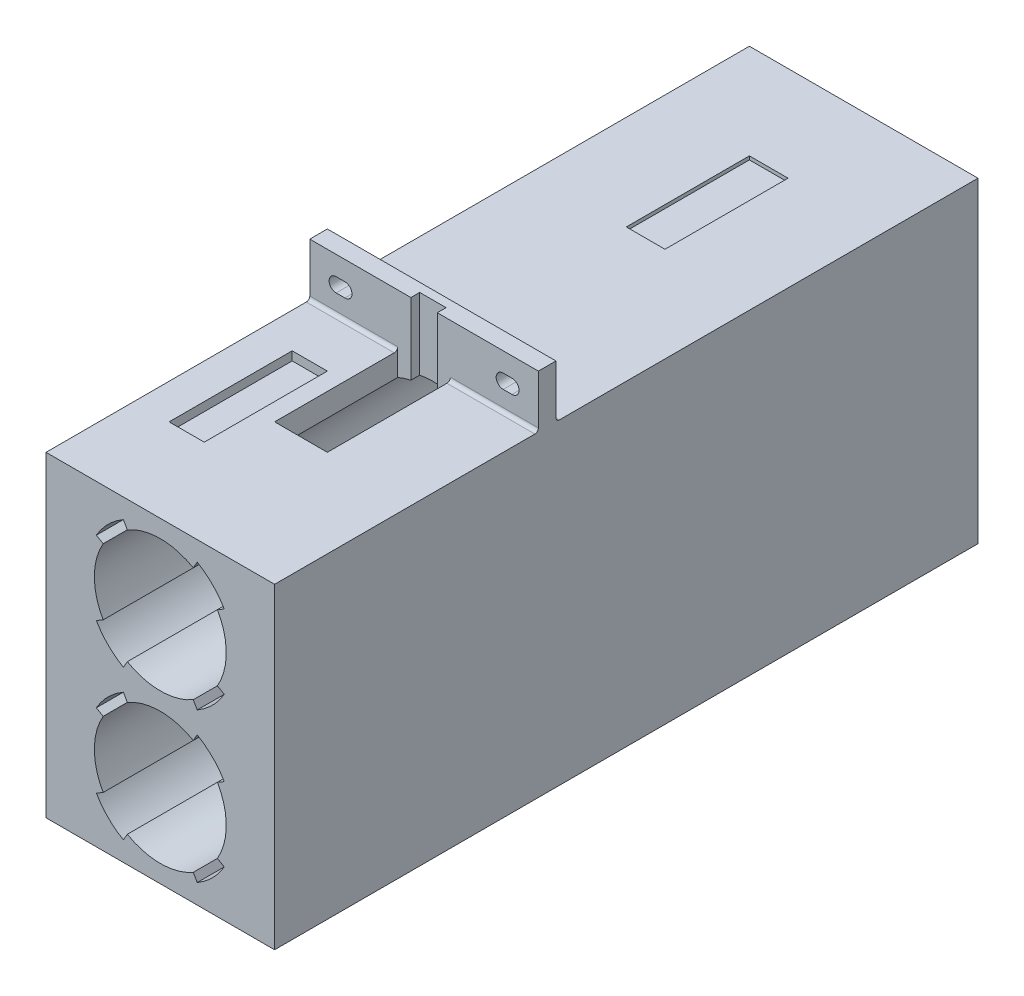
SolidWorks part; units mm, degrees
ref_plane "前基準面" through (0, 0, 0) normal (0, 0, 1) x (1, 0, 0)
ref_plane "上基準面" through (0, 0, 0) normal (0, 1, 0) x (1, 0, 0)
ref_plane "右基準面" through (0, 0, 0) normal (1, 0, 0) x (0, 0, -1)
ref_axis "基準軸1" through (0, -55, 0) along (0, 1, 0)
ref_axis "基準軸2" through (-88.99, 0, 0) along (1, 0, 0)
ref_axis "基準軸3" through (0, 0, 55) along (0, 0, -1)
sketch "草圖1" plane through (0, 0, 0) normal (0, 0, 1) x (1, 0, 0)
  line L1 (-130, 0) -> (0, 0)
  line L2 (-130, 0) -> (-130, 180)
  line L3 (-130, 180) -> (0, 180)
  line L4 (0, 0) -> (0, 180)
  dimension "D1" = 180
  dimension "D2" = 130
extrude "填料-伸長1" add sketch "草圖1" along normal blind 400
sketch "草圖2" plane through (0, 0, 400) normal (0, 0, 1) x (1, 0, 0)
  line L0 (0, 0) -> (0, 180) construction
  line L1 (0, 180) -> (-130, 180) construction
  line L2 (-130, 0) -> (0, 0) construction
  circle A0 centre (-65, 132.5) radius 37.5
  circle A1 centre (-65, 47.5) radius 37.5
  dimension "D4" = 75
  dimension "D5" = 75
  dimension "D1" = 65
  dimension "D2" = 47.5
  dimension "D3" = 47.5
extrude "除料-伸長1" cut sketch "草圖2" against normal through all
ref_plane "平面2" through (0, 0, 5) normal (0, 0, -1) x (-1, 0, 0)
ref_axis "基準軸4" through (-65, 132.5, 0) along (0, 0, 1)
ref_plane "平面1" through (0, 90, 0) normal (0, 1, 0) x (1, 0, 0)
sketch "草圖11" plane through (0, 180, 0) normal (0, 1, 0) x (1, 0, 0)
  line L0 (-65, -400) -> (-65, 46.2584) construction
  line L1 (0, -400) -> (-130, -400) construction
  line L3 (-50, -250) -> (-80, -250)
  line L4 (-50, -250) -> (-50, -320)
  line L6 (-80, -250) -> (-80, -320)
  line L7 (-65, -350) -> (-65, -250) construction
  line L8 (-40, -300) -> (-90, -300) construction
  line L10 (-50, -320) -> (-80, -320)
  point P4 (-65, -300)
  dimension "D1" = 30
  dimension "D2" = 50
  dimension "D3" = 100
  dimension "D4" = 70
extrude "除料-伸長4" cut sketch "草圖11" against normal up to next
sketch "草圖12" plane through (0, 180, 0) normal (0, 1, 0) x (1, 0, 0)
  line L0 (-130, -400) -> (-130, 0) construction
  line L8 (-65, -252.5) -> (-65, -317.5) construction
  line L14 (-110, -280) -> (-90, -280)
  line L15 (-110, -280) -> (-110, -350)
  line L16 (-110, -350) -> (-90, -350)
  line L17 (-50, -320) -> (-50, -250) construction
  line L18 (-80, -320) -> (-50, -320) construction
  line L19 (-50, -250) -> (-80, -250) construction
  line L20 (-50, -250) -> (-80, -250) construction
  line L21 (-80, -320) -> (-50, -320) construction
  line L22 (-50, -320) -> (-50, -250) construction
  line L23 (-90, -280) -> (-90, -350)
  point P1 (-65, -250)
  dimension "D1" = 20
  dimension "D2" = 70
  dimension "D3" = 30
  dimension "D4" = 20
extrude "除料-伸長5" cut sketch "草圖12" against normal blind 5
sketch "草圖13" plane through (0, 180, 0) normal (0, 1, 0) x (1, 0, 0)
  line L0 (0, -55) -> (0, 55) construction
  line L1 (0, 0) -> (-130, 0) construction
  line L5 (0, -99) -> (0, 99) construction
  line L6 (-76, -54) -> (-54, -54)
  line L7 (-54, -124) -> (-76, -124)
  line L8 (-65, 0) -> (-65, -72) construction
  line L9 (-130, 0) -> (-130, 70) construction
  line L10 (-130, 70) -> (0, 70) construction
  line L11 (0, 70) -> (0, 0) construction
  line L13 (-130, -400) -> (-130, 0) construction
  line L15 (0, 0) -> (-130, 0) construction
  line L16 (-54, -124) -> (-54, -54)
  line L20 (-76, -54) -> (-76, -124)
  line L21 (-65, -83.1553) -> (-65, -60.8447) construction
  circle A1 centre (-65, -11) radius 7 construction
  circle A2 centre (-65, -72) radius 1.1 construction
  point P10 (-65, -18)
  point P23 (-65, -54)
  dimension "D2" = 22
  dimension "D3" = 14
  dimension "D6" = 2.2
  dimension "D1" = 70
  dimension "D4" = 18
  dimension "D5" = 54
  dimension "D7" = 70
  dimension "D8" = 18
extrude "除料-伸長6" cut sketch "草圖13" against normal blind 2
sketch "草圖14" plane through (0, 180, 0) normal (0, 1, 0) x (1, 0, 0)
  line L0 (-130, -400) -> (-130, 0) construction
  line L1 (-130, -250) -> (0, -250)
  line L2 (-130, -250) -> (-130, -240)
  line L3 (-130, -240) -> (0, -240)
  line L4 (0, -250) -> (0, -240)
  line L5 (0, -400) -> (0, 0) construction
  line L6 (-50, -250) -> (-80, -250) construction
  dimension "D1" = 10
extrude "填料-伸長6" add sketch "草圖14" along normal blind 30
sketch "草圖15" plane through (0, 0, 250) normal (0, 0, 1) x (1, 0, 0)
  line L0 (-115, 195) -> (-15, 195) construction
  line L2 (-115, 191) -> (-110, 191)
  line L3 (-130, 210) -> (0, 210) construction
  line L6 (-65, 210) -> (-65, 176.5513) construction
  line L9 (-15, 191) -> (-20, 191)
  line L10 (-15, 199) -> (-20, 199)
  line L11 (-110, 199) -> (-115, 199)
  arc A0 (-115, 199) -> (-115, 191) centre (-115, 195) ccw
  arc A2 (-110, 199) -> (-110, 191) centre (-110, 195) cw
  arc A4 (-20, 199) -> (-20, 191) centre (-20, 195) ccw
  arc A5 (-15, 199) -> (-15, 191) centre (-15, 195) cw
  point P2 (-65, 195)
  point P9 (-65, 210)
  dimension "D1" = 4
  dimension "D4" = 5
  dimension "D5" = 8
  dimension "D2" = 100
  dimension "D3" = 15
extrude "除料-伸長7" cut sketch "草圖15" against normal up to next
sketch "草圖16" plane through (0, 210, 0) normal (0, 1, 0) x (1, 0, 0)
  line L0 (-65, -250) -> (-65, -272.9233) construction
  line L1 (-130, -250) -> (0, -250) construction
  line L3 (-57.5, -245) -> (-72.5, -245)
  line L4 (-57.5, -245) -> (-57.5, -250)
  line L5 (-57.5, -250) -> (-72.5, -250)
  line L6 (-72.5, -245) -> (-72.5, -250)
  line L7 (-65, -250) -> (-65, -245) construction
  line L8 (-57.5, -247.5) -> (-72.5, -247.5) construction
  point P4 (-65, -247.5)
  dimension "D1" = 15
  dimension "D2" = 5
extrude "除料-伸長8" cut sketch "草圖16" against normal up to surface (40.7577 mm away) up to face at (-65, 168.4347, 285)
fillet "圓角1" radius 2 3 edges at (-65, 180, 240) (-25, 180, 250) (-105, 180, 250)
sketch "草圖17" plane through (0, 0, 400) normal (0, 0, 1) x (1, 0, 0)
  line L2 (-65, 132.5) -> (-65, 47.5) construction
  line L3 (16.636, 90) -> (-161.4893, 90) construction
  line L4 (-44, 83.8731) -> (-46.5, 79.5429)
  line L5 (-28.6269, 68.5) -> (-32.9571, 66)
  line L6 (-44, 168.8731) -> (-46.5, 164.5429)
  line L7 (-28.6269, 153.5) -> (-32.9571, 151)
  line L8 (-28.6269, 111.5) -> (-32.9571, 114)
  line L9 (-44, 96.1269) -> (-46.5, 100.4571)
  line L10 (-86, 96.1269) -> (-83.5, 100.4571)
  line L11 (-101.3731, 111.5) -> (-97.0429, 114)
  line L12 (-101.3731, 153.5) -> (-97.0429, 151)
  line L13 (-86, 168.8731) -> (-83.5, 164.5429)
  line L14 (-28.6269, 26.5) -> (-32.9571, 29)
  line L15 (-44, 11.1269) -> (-46.5, 15.4571)
  line L16 (-86, 11.1269) -> (-83.5, 15.4571)
  line L17 (-101.3731, 26.5) -> (-97.0429, 29)
  line L18 (-101.3731, 68.5) -> (-97.0429, 66)
  line L19 (-86, 83.8731) -> (-83.5, 79.5429)
  circle A2 centre (-65, 132.5) radius 37.5 construction
  circle A3 centre (-65, 132.5) radius 37.5 construction
  circle A4 centre (-65, 47.5) radius 37.5 construction
  circle A5 centre (-65, 47.5) radius 37.5 construction
  arc A6 (-32.9571, 66) -> (-46.5, 79.5429) centre (-65, 47.5) ccw
  arc A7 (-28.6269, 68.5) -> (-44, 83.8731) centre (-65, 47.5) ccw
  arc A8 (-32.9571, 151) -> (-46.5, 164.5429) centre (-65, 132.5) ccw
  arc A9 (-28.6269, 153.5) -> (-44, 168.8731) centre (-65, 132.5) ccw
  arc A10 (-46.5, 100.4571) -> (-32.9571, 114) centre (-65, 132.5) ccw
  arc A11 (-44, 96.1269) -> (-28.6269, 111.5) centre (-65, 132.5) ccw
  arc A12 (-97.0429, 114) -> (-83.5, 100.4571) centre (-65, 132.5) ccw
  arc A13 (-101.3731, 111.5) -> (-86, 96.1269) centre (-65, 132.5) ccw
  arc A14 (-83.5, 164.5429) -> (-97.0429, 151) centre (-65, 132.5) ccw
  arc A15 (-86, 168.8731) -> (-101.3731, 153.5) centre (-65, 132.5) ccw
  arc A16 (-46.5, 15.4571) -> (-32.9571, 29) centre (-65, 47.5) ccw
  arc A17 (-44, 11.1269) -> (-28.6269, 26.5) centre (-65, 47.5) ccw
  arc A18 (-97.0429, 29) -> (-83.5, 15.4571) centre (-65, 47.5) ccw
  arc A19 (-101.3731, 26.5) -> (-86, 11.1269) centre (-65, 47.5) ccw
  arc A20 (-83.5, 79.5429) -> (-97.0429, 66) centre (-65, 47.5) ccw
  arc A21 (-86, 83.8731) -> (-101.3731, 68.5) centre (-65, 47.5) ccw
  point P9 (-65, 90)
  point P32 (-65, 132.5)
  point P45 (-65, 47.5)
  dimension "D3" = 30
  dimension "D4" = 37
  dimension "D7" = 30
  dimension "D10" = 42
  dimension "D11" = 37
  dimension "D5" = 42
  dimension "D6" = 5
  dimension "D9" = 5
  dimension "D12" = 60
  dimension "D13" = 60
  dimension "D2" = 30
  dimension "D8" = 30
  dimension "D14" = 4
  dimension "D15" = 4
extrude "除料-伸長9" cut sketch "草圖17" against normal through all
